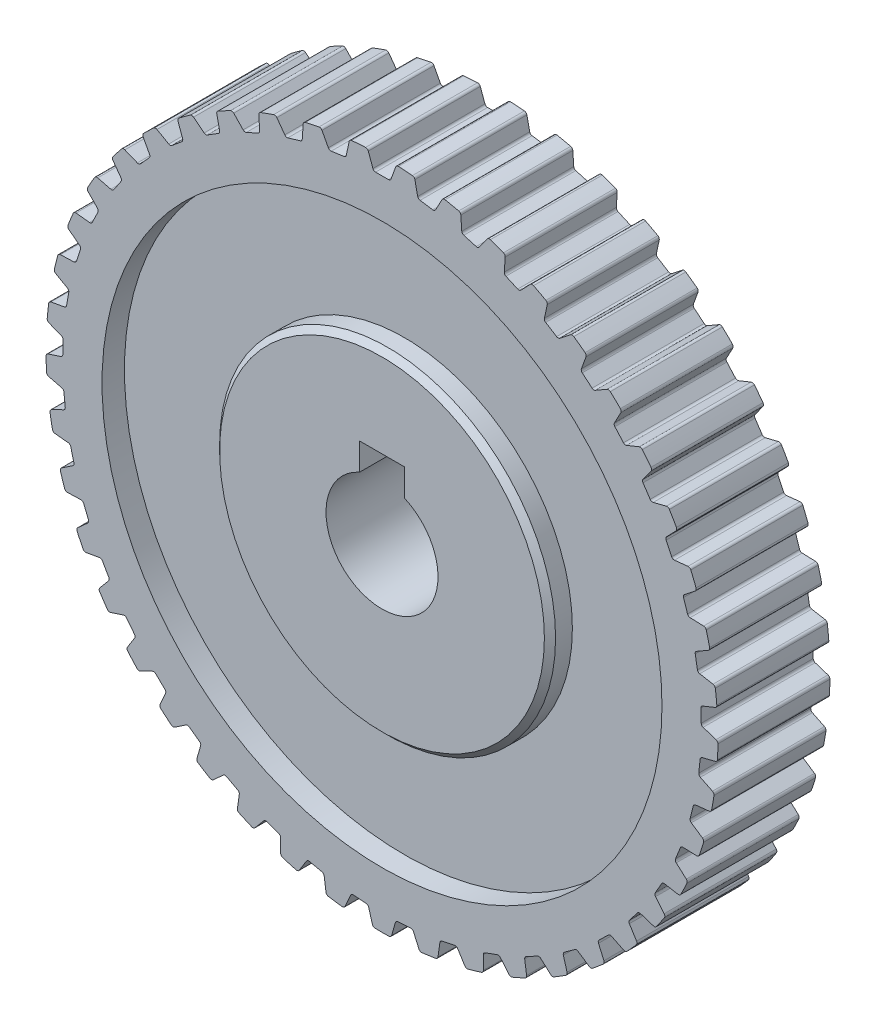
SolidWorks part; units mm, degrees
ref_plane "Front Plane" through (0, 0, 0) normal (0, 0, 1) x (1, 0, 0)
ref_plane "Top Plane" through (0, 0, 0) normal (0, 1, 0) x (1, 0, 0)
ref_plane "Right Plane" through (0, 0, 0) normal (1, 0, 0) x (0, 0, -1)
sketch "Sketch1" plane through (0, 0, 0) normal (0, 0, 1) x (1, 0, 0)
  line L1 (0, 5) -> (0, 6.9445) construction
  line L3 (-2, 4.5826) -> (-2, 7)
  line L4 (-2, 7) -> (2, 7)
  line L5 (2, 4.5826) -> (2, 7)
  line L6 (-0.1095, 4.9988) -> (0, 5.1027) construction
  line L7 (0, 5.1027) -> (0.1095, 4.9988) construction
  circle A0 centre (0, 0) radius 30
  arc A1 (-2, 4.5826) -> (2, 4.5826) centre (0, 0) ccw
  arc A2 (0.1095, 4.9988) -> (-0.1095, 4.9988) centre (0, 0) ccw
  point P4 (0, 5.1027)
  dimension "D1" = 60
  dimension "D2" = 10
  dimension "D3" = 4
  dimension "D4" = 7
extrude "Boss-Extrude1" add sketch "Sketch1" along normal blind 10 contours A0 A1 L3 L4 L5 region at (-29.1515, 0, 0)
sketch "Sketch2" plane through (0, 0, 10) normal (0, 0, 1) x (1, 0, 0)
  line L0 (0, 0) -> (0, 34.8507) construction
  line L1 (1.2859, 29.9724) -> (0.75, 28.5)
  line L2 (0.75, 28.5) -> (-0.75, 28.5)
  line L3 (-0.75, 28.5) -> (-1.2859, 29.9724)
  circle A0 centre (0, 0) radius 30 construction
  circle A1 centre (0, 0) radius 30
  circle M9 centre (0, 0) radius 30
  dimension "D1" = 20
  dimension "D2" = 20
  dimension "D3" = 1.5
  dimension "D4" = 28.5
extrude "Cut-Extrude2" cut sketch "Sketch2" against normal through all contours L2 L0 A1 L3 | L0 L2 L1 M9 region at (-0.5201, 29.3114, 10) region at (0.5201, 29.3114, 10)
pattern_circular "CirPattern1" count 45 over 360 about axis through (0, 0, 10) along (0, 0, -1) of "Cut-Extrude2" reverse direction yes
sketch "Sketch3" plane through (0, 0, 10) normal (0, 0, 1) x (1, 0, 0)
  circle A0 centre (0, 0) radius 25
  dimension "D1" = 50
extrude "Cut-Extrude-Thin1" cut sketch "Sketch3" against normal blind 2 thin thin type one direction reverse wall 10
chamfer "Chamfer1" distance 0.5 angle 45 1 edges at (15, 0, 10)
ref_plane "Plane1" through (0, 0, 5) normal (0, 0, 1) x (1, 0, 0)
mirror "Mirror1" about plane through (0, 0, 5) normal (0, 0, 1) of "Cut-Extrude-Thin1"
chamfer "Chamfer2" distance 0.5 angle 45 1 edges at (15, 0, 0)
fillet "Fillet1" radius 0.25 180 edges at (29.9427, -1.8541, 5) (13.3656, 26.8581, 5) (12.2772, 25.731, 5) (10.9068, 26.3411, 5) (11.0161, 27.9042, 5) (9.4976, 28.4569, 5) (8.5766, 27.1892, 5) (7.1347, 27.6027, 5) (7.0254, 29.1658, 5) (5.4448, 29.5018, 5) (4.7091, 28.1183, 5) (3.2237, 28.327, 5) (2.898, 29.8597, 5) (1.2859, 29.9724, 5) (0.75, 28.5, 5) (-0.75, 28.5, 5) (-1.2859, 29.9724, 5) (-2.898, 29.8597, 5) (-3.2237, 28.327, 5) (-4.7091, 28.1183, 5) (-5.4448, 29.5018, 5) (-7.0254, 29.1658, 5) (-7.1347, 27.6027, 5) (-8.5766, 27.1892, 5) (-9.4976, 28.4569, 5) (-11.0161, 27.9042, 5) (-10.9068, 26.3411, 5) (-12.2772, 25.731, 5) (-13.3656, 26.8581, 5) (-14.7924, 26.0995, 5) (-14.4667, 24.5668, 5) (-15.7387, 23.7719, 5) (-16.9735, 24.7366, 5) (-18.2808, 23.7868, 5) (-17.7449, 22.3144, 5) (-18.894, 21.3502, 5) (-20.251, 22.1336, 5) (-21.4134, 21.0111, 5) (-20.6778, 19.6276, 5) (-21.6815, 18.5129, 5) (-23.1343, 19.0998, 5) (-24.1292, 17.8264, 5) (-23.2082, 16.5588, 5) (-24.047, 15.3152, 5) (-25.5673, 15.6943, 5) (-26.3753, 14.2948, 5) (-25.2869, 13.1677, 5) (-25.9444, 11.8195, 5) (-27.5027, 11.9833, 5) (-28.1081, 10.485, 5) (-26.8733, 9.5203, 5) (-27.3369, 8.0937, 5) (-28.9028, 8.039, 5) (-29.2938, 6.471, 5) (-27.9368, 5.6876, 5) (-28.1973, 4.2104, 5) (-29.7404, 3.9383, 5) (-29.9093, 2.3312, 5) (-28.4565, 1.7442, 5) (-28.5088, 0.2451, 5) (-29.999, -0.2391, 5) (-29.9427, -1.8541, 5) (-28.4223, -2.2332, 5) (-28.2655, -3.725, 5) (-29.6738, -4.4118, 5) (-29.3932, -6.0033, 5) (-27.8349, -6.1671, 5) (-27.472, -7.6225, 5) (-28.771, -8.4987, 5) (-28.2717, -10.0356, 5) (-26.7057, -9.9809, 5) (-26.1438, -11.3717, 5) (-27.3082, -12.4202, 5) (-26.5998, -13.8726, 5) (-25.0567, -13.6005, 5) (-24.3067, -14.8995, 5) (-25.3139, -16.0999, 5) (-24.4103, -17.4396, 5) (-22.9201, -16.9553, 5) (-21.9966, -18.1374, 5) (-22.8269, -19.4662, 5) (-21.7456, -20.6671, 5) (-20.3373, -19.9802, 5) (-19.2583, -21.0222, 5) (-19.8956, -22.4536, 5) (-18.6577, -23.4924, 5) (-17.3586, -22.6161, 5) (-16.1451, -23.4978, 5) (-16.577, -25.004, 5) (-15.2066, -25.8604, 5) (-14.0422, -24.8119, 5) (-12.7177, -25.5161, 5) (-12.9358, -27.0678, 5) (-11.4595, -27.7251, 5) (-10.4523, -26.5247, 5) (-9.0428, -27.0378, 5) (-9.0428, -28.6047, 5) (-7.4894, -29.0501, 5) (-6.6591, -27.7213, 5) (-5.1919, -28.0331, 5) (-4.9738, -29.5848, 5) (-3.3736, -29.8097, 5) (-2.7362, -28.3783, 5) (-1.2399, -28.4829, 5) (-0.808, -29.9891, 5) (0.808, -29.9891, 5) (1.2399, -28.4829, 5) (2.7362, -28.3783, 5) (3.3736, -29.8097, 5) (4.9738, -29.5848, 5) (5.1919, -28.0331, 5) (6.6591, -27.7213, 5) (7.4894, -29.0501, 5) (9.0428, -28.6047, 5) (9.0428, -27.0378, 5) (10.4523, -26.5247, 5) (11.4595, -27.7251, 5) (12.9358, -27.0678, 5) (12.7177, -25.5161, 5) (14.0422, -24.8119, 5) (15.2066, -25.8604, 5) (16.577, -25.004, 5) (16.1451, -23.4978, 5) (17.3586, -22.6161, 5) (18.6577, -23.4924, 5) (19.8956, -22.4536, 5) (19.2583, -21.0222, 5) (20.3373, -19.9802, 5) (21.7456, -20.6671, 5) (22.8269, -19.4662, 5) (21.9966, -18.1374, 5) (22.9201, -16.9553, 5) (24.4103, -17.4396, 5) (25.3139, -16.0999, 5) (25.0567, -13.6005, 5) (24.3067, -14.8995, 5) (26.5998, -13.8726, 5) (26.1438, -11.3717, 5) (27.3082, -12.4202, 5) (26.7057, -9.9809, 5) (28.2717, -10.0356, 5) (28.771, -8.4987, 5) (27.472, -7.6225, 5) (27.8349, -6.1671, 5) (29.3932, -6.0033, 5) (29.6738, -4.4118, 5) (28.2655, -3.725, 5) (28.4223, -2.2332, 5) (29.999, -0.2391, 5) (28.5088, 0.2451, 5) (28.4565, 1.7442, 5) (29.9093, 2.3312, 5) (29.7404, 3.9383, 5) (28.1973, 4.2104, 5) (27.9368, 5.6876, 5) (29.2938, 6.471, 5) (28.9028, 8.039, 5) (27.3369, 8.0937, 5) (26.8733, 9.5203, 5) (28.1081, 10.485, 5) (27.5027, 11.9833, 5) (25.9444, 11.8195, 5) (25.2869, 13.1677, 5) (26.3753, 14.2948, 5) (25.5673, 15.6943, 5) (24.047, 15.3152, 5) (23.2082, 16.5588, 5) (24.1292, 17.8264, 5) (23.1343, 19.0998, 5) (21.6815, 18.5129, 5) (20.6778, 19.6276, 5) (21.4134, 21.0111, 5) (20.251, 22.1336, 5) (18.894, 21.3502, 5) (17.7449, 22.3144, 5) (18.2808, 23.7868, 5) (14.7924, 26.0995, 5) (15.7387, 23.7719, 5) (14.4667, 24.5668, 5) (16.9735, 24.7366, 5)
